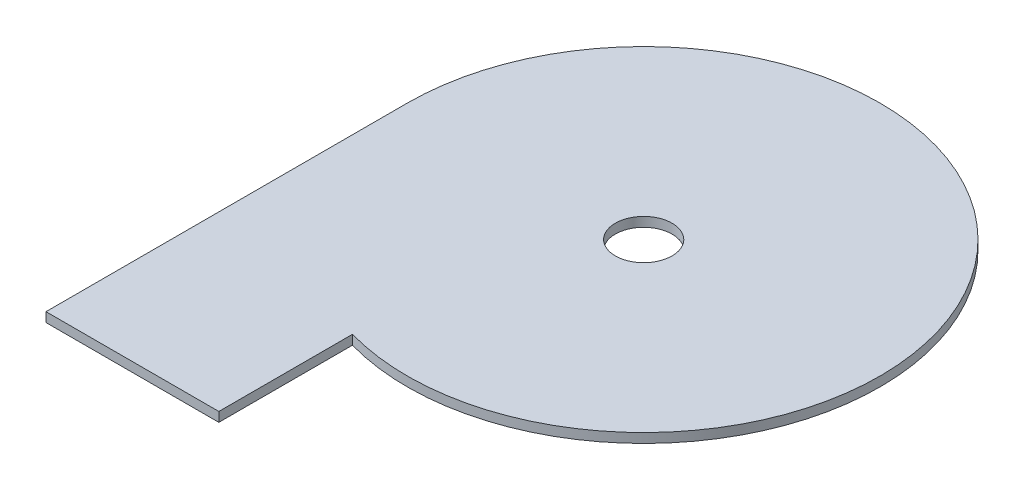
SolidWorks part; units mm, degrees
ref_plane "Front Plane" through (0, 0, 0) normal (0, 0, 1) x (1, 0, 0)
ref_plane "Top Plane" through (0, 0, 0) normal (0, 1, 0) x (1, 0, 0)
ref_plane "Right Plane" through (0, 0, 0) normal (1, 0, 0) x (0, 0, -1)
sketch "Sketch1" plane through (0, 0, 0) normal (0, 1, 0) x (1, 0, 0)
  circle A0 centre (0, 0) radius 50
extrude "Boss-Extrude1" add sketch "Sketch1" along normal blind 2
sketch "Sketch2" plane through (0, 2, 0) normal (0, 1, 0) x (1, 0, 0)
  circle A0 centre (0, 0) radius 6
extrude "Cut-Extrude1" cut sketch "Sketch2" against normal blind 2
sketch "Sketch3" plane through (0, 0, 0) normal (0, -1, 0) x (1, 0, 0)
  line L1 (-50, 0) -> (-13.4445, 0)
  line L2 (-50, 0) -> (-50, 76.4199)
  line L3 (-50, 76.4199) -> (-13.4445, 76.4199)
  line L4 (-13.4445, 0) -> (-13.4445, 76.4199)
  circle A0 centre (0, 0) radius 50 construction
extrude "Boss-Extrude2" add sketch "Sketch3" against normal through all
sketch "Sketch4" plane through (0, 2, 0) normal (0, 1, 0) x (1, 0, 0)
  line L4 (-26, -48.23) -> (-26, -61.13)
  line L5 (-20.1, -48.23) -> (-26, -48.23)
  line L6 (-20.1, -61.13) -> (-20.1, -48.23)
  line L7 (-26, -61.13) -> (-20.1, -61.13)
  line L8 (-26, -48.23) -> (-26, -61.13)
  line L9 (-20.1, -48.23) -> (-26, -48.23)
  line L10 (-20.1, -61.13) -> (-20.1, -48.23)
  line L11 (-26, -61.13) -> (-20.1, -61.13)
  dimension "D1" = 0
